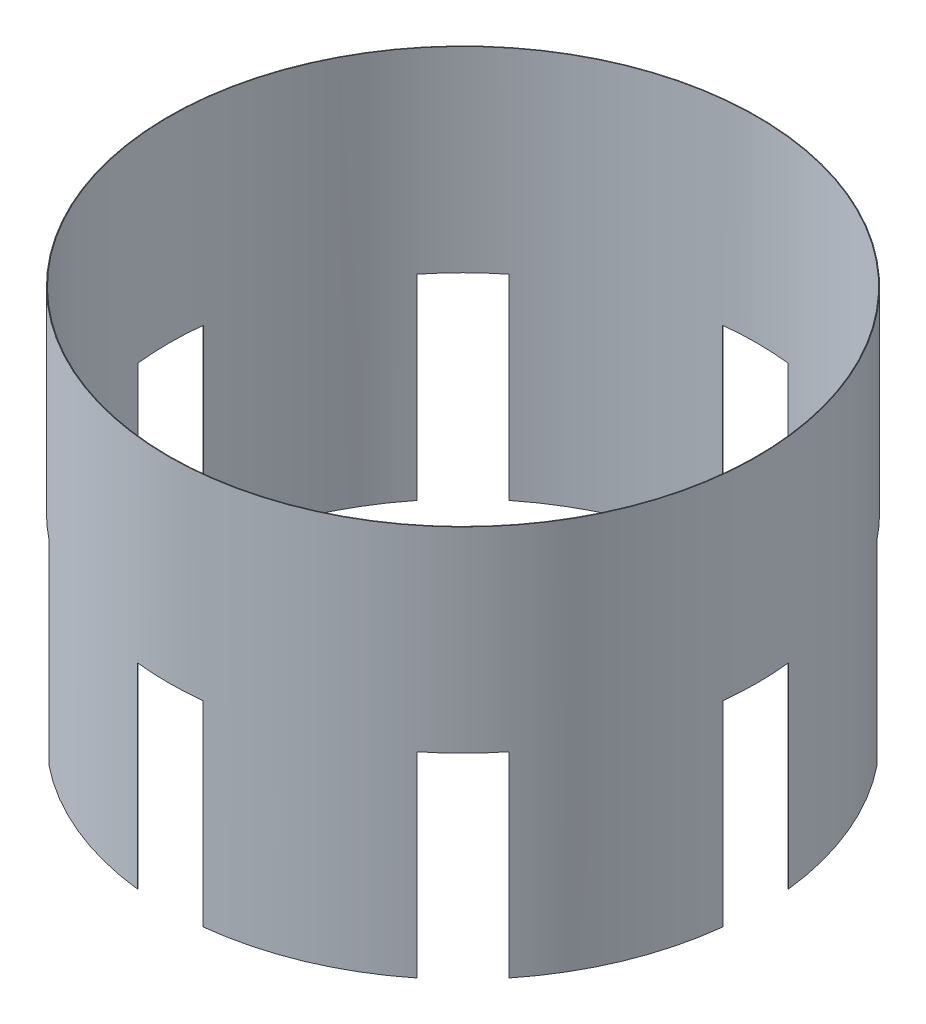
SolidWorks part; units mm, degrees
ref_plane "Front Plane" through (0, 0, 0) normal (0, 0, 1) x (1, 0, 0)
ref_plane "Top Plane" through (0, 0, 0) normal (0, 1, 0) x (1, 0, 0)
ref_plane "Right Plane" through (0, 0, 0) normal (1, 0, 0) x (0, 0, -1)
ref_plane "Plane1" through (0, 1200, 0) normal (0, 1, 0) x (1, 0, 0)
sketch "Sketch1" plane through (0, 1200, 0) normal (0, 1, 0) x (1, 0, 0)
  circle A0 centre (0, 0) radius 450
  circle A2 centre (0, 0) radius 451
extrude "Boss-Extrude1" add sketch "Sketch1" along normal blind 600
ref_axis "Axis1" through (0, 1167.8, 0) along (0, 1, 0)
sketch "Sketch10" plane through (0, 0, 0) normal (0, 0, 1) x (1, 0, 0)
  line L0 (0, 1200) -> (0, 1559.6312) construction
  line L5 (-793.3392, 1350) -> (49206.6608, 1350) construction
  line L6 (50, 1500) -> (50, 1200)
  line L7 (-451, 1200) -> (451, 1200) construction
  line L8 (50, 1200) -> (-50, 1200)
  line L9 (-50, 1200) -> (-50, 1500)
  line L10 (-50, 1500) -> (50, 1500)
extrude "Cut-Extrude1" cut sketch "Sketch10" against normal through all both and the other way through all
pattern_circular "CirPattern1" count 4 every 45 about axis through (0, 1167.8, 0) along (0, 1, 0) of "Cut-Extrude1"
